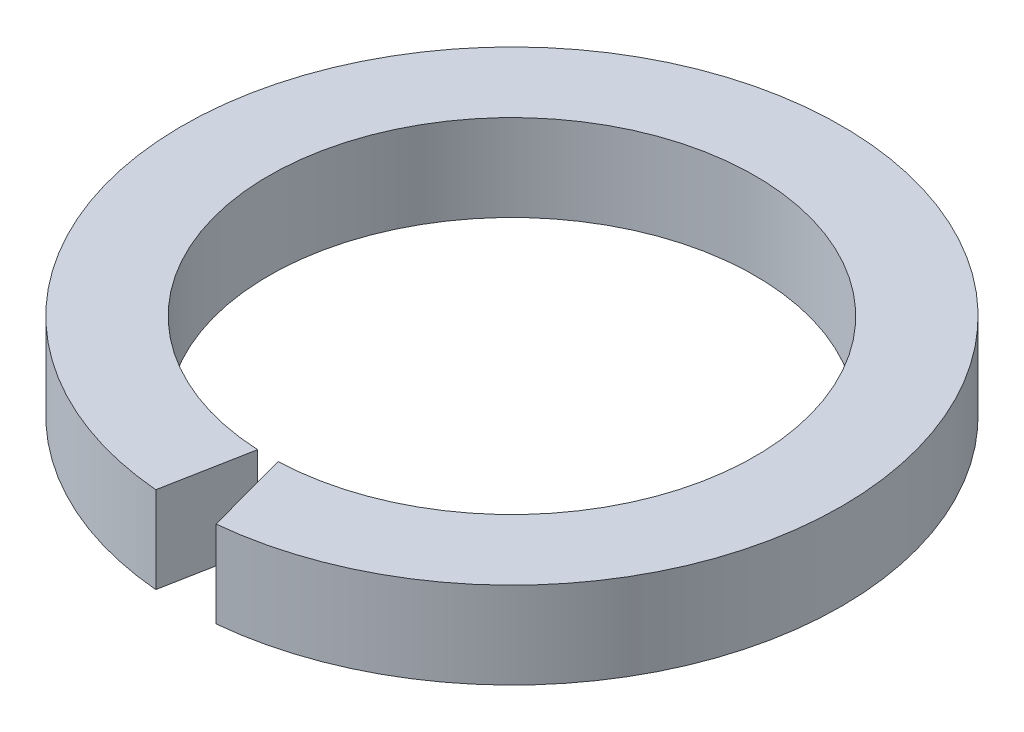
SolidWorks part; units mm, degrees
ref_plane "Front Plane" through (0, 0, 0) normal (0, 0, 1) x (1, 0, 0)
ref_plane "Top Plane" through (0, 0, 0) normal (0, 1, 0) x (1, 0, 0)
ref_plane "Right Plane" through (0, 0, 0) normal (1, 0, 0) x (0, 0, -1)
sketch "Sketch1" plane through (0, 0, 0) normal (0, 1, 0) x (1, 0, 0)
  circle A0 centre (0, 0) radius 14.05
  circle A1 centre (0, 0) radius 19.05
extrude "Boss-Extrude1" add sketch "Sketch1" along normal blind 5
sketch "Sketch3" plane through (0, 0, 0) normal (0, 1, 0) x (1, 0, 0)
  line L0 (0, 0) -> (0, -27.1481) construction
  line L1 (-1.8157, -20.1156) -> (2.1678, -20.1156)
  line L2 (0, -13.2077) -> (-0.506, -13.2077)
  line L3 (0, -13.2077) -> (0.3101, -13.2077)
  line L4 (0.3101, -13.2077) -> (2.1678, -20.1156)
  line L5 (-1.8157, -20.1156) -> (-0.506, -13.2077)
extrude "Cut-Extrude2" cut sketch "Sketch3" against normal blind 12 and the other way blind 15
